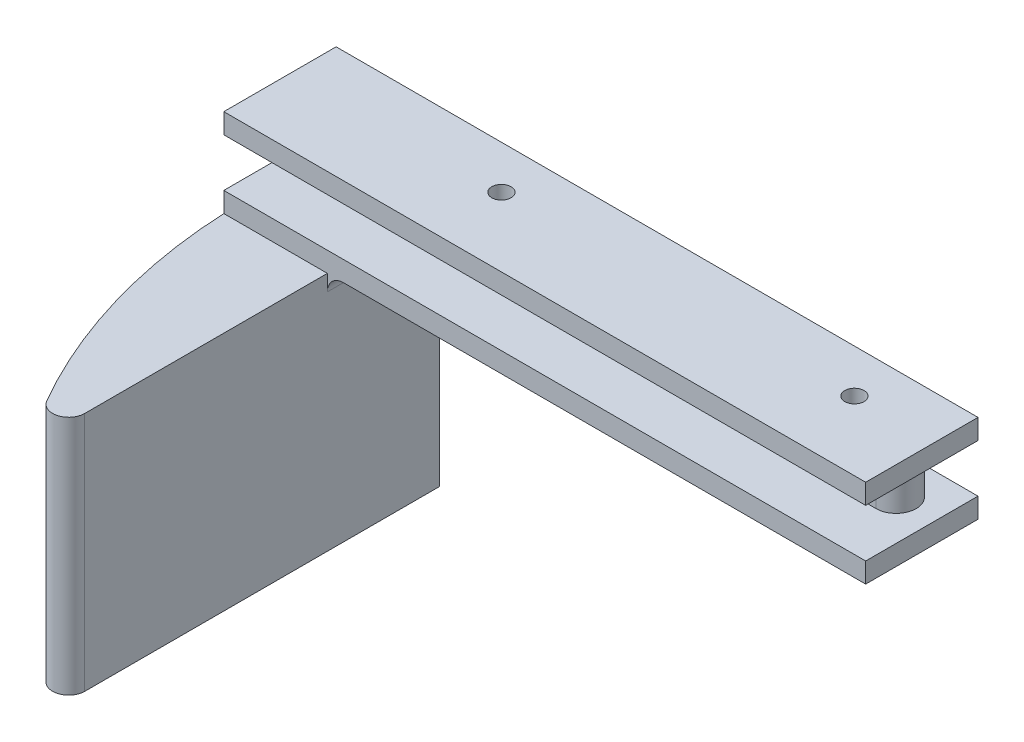
SolidWorks part; units mm, degrees
ref_plane "Front Plane" through (0, 0, 0) normal (0, 0, 1) x (1, 0, 0)
ref_plane "Top Plane" through (0, 0, 0) normal (0, 1, 0) x (1, 0, 0)
ref_plane "Right Plane" through (0, 0, 0) normal (1, 0, 0) x (0, 0, -1)
sketch "Sketch2" plane through (0, 0, 0) normal (0, 1, 0) x (1, 0, 0)
  line L1 (0, 0) -> (101.6, 0)
  line L2 (0, 0) -> (0, 17.78)
  line L3 (0, 17.78) -> (101.6, 17.78)
  line L4 (101.6, 0) -> (101.6, 17.78)
  dimension "D1" = 17.78
  dimension "D2" = 101.6
extrude "Boss-Extrude1" add sketch "Sketch2" along normal blind 3.175
sketch "Sketch3" plane through (0, 0, 0) normal (0, -1, 0) x (1, 0, 0)
  line L0 (95.25, -11.176) -> (6.35, -11.176) construction
  line L1 (95.25, -14.351) -> (6.35, -14.351)
  line L2 (95.25, -8.001) -> (6.35, -8.001)
  line L3 (0, 0) -> (101.6, 0) construction
  line L4 (0, -17.78) -> (0, 0) construction
  arc A0 (95.25, -14.351) -> (95.25, -8.001) centre (95.25, -11.176) ccw
  arc A1 (6.35, -8.001) -> (6.35, -14.351) centre (6.35, -11.176) ccw
  point P2 (50.8, -11.176)
  dimension "D1" = 88.9
  dimension "D2" = 11.176
  dimension "D3" = 6.35
  dimension "D4" = 6.35
extrude "Boss-Extrude2" add sketch "Sketch3" along normal blind 7.62 contours L2 A1 L1 A0
ref_plane "Plane1" through (0, -3.81, 0) normal (0, -1, 0) x (-1, 0, 0)
mirror "Mirror1" about plane through (0, -3.81, 0) normal (0, -1, 0) of "Boss-Extrude1"
sketch "Sketch4" plane through (0, -10.795, 0) normal (0, -1, 0) x (1, 0, 0)
  line L0 (0, 0) -> (101.6, 0) construction
  line L1 (0, -17.78) -> (16.3938, -17.78)
  line L2 (0, -17.78) -> (0, 0)
  line L4 (16.3938, -17.78) -> (16.3938, 0)
  line L5 (16.3938, 0) -> (16.3938, 47.009)
  arc A0 (0, 0) -> (16.3938, 47.009) centre (87.5, -4.1516) cw
extrude "Boss-Extrude3" add sketch "Sketch4" along normal blind 38.1
fillet "Fillet1" radius 2.54 1 edges at (16.3938, -10.795, -8.89)
fillet "Fillet2" radius 2.54 1 edges at (16.3938, -29.845, 47.009)
sketch "Sketch5" plane through (0, -10.795, 0) normal (0, -1, 0) x (-1, 0, 0)
  line L0 (-101.6, 0) -> (-101.6, 17.78) construction
  line L2 (-101.6, 17.78) -> (-18.9338, 17.78) construction
  circle A0 centre (-88.9, 10.922) radius 1.524
  circle A1 centre (-33.02, 10.922) radius 1.524
  dimension "D1" = 3.048
  dimension "D2" = 3.048
  dimension "D3" = 12.7
  dimension "D4" = 55.88
  dimension "D5" = 6.858
extrude "Cut-Extrude1" cut sketch "Sketch5" against normal through all
